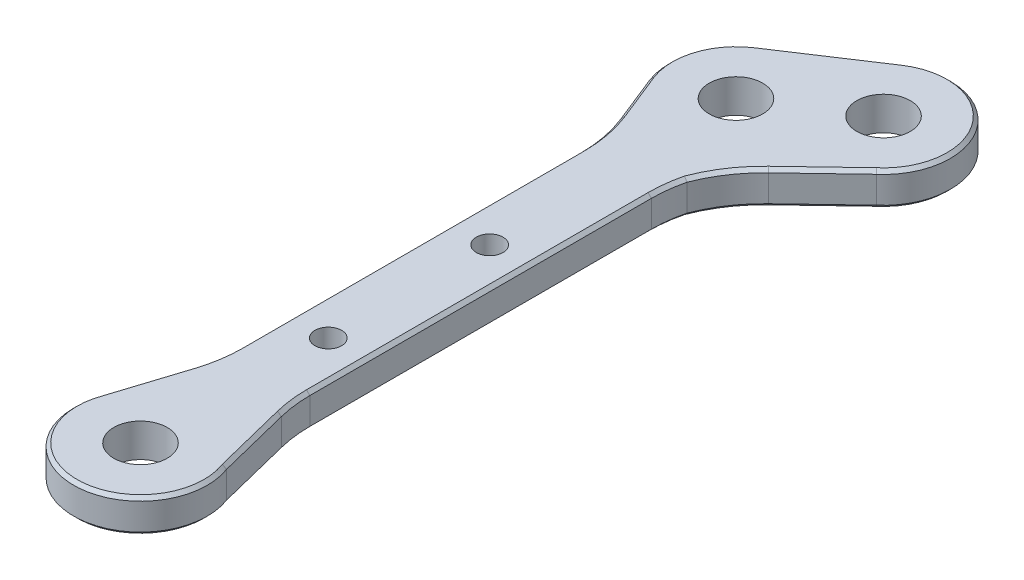
SolidWorks part; units mm, degrees
material "5052-O"
ref_plane "正面" through (0, 0, 0) normal (0, 0, 1) x (1, 0, 0)
ref_plane "平面" through (0, 0, 0) normal (0, 1, 0) x (1, 0, 0)
ref_plane "右側面" through (0, 0, 0) normal (1, 0, 0) x (0, 0, -1)
sketch "ｽｹｯﾁ1" plane through (0, 0, 0) normal (0, 1, 0) x (1, 0, 0)
  line L0 (-31.2667, 475.4743) -> (17.7329, 475.685) construction
  line L1 (29.4015, 408.0828) -> (36.0548, 412.4694)
  line L2 (29.6332, 396.7526) -> (27.4704, 402.1573)
  line L3 (29.6332, 396.7526) -> (29.6332, 367.7526)
  line L4 (29.6332, 367.7526) -> (27.5048, 361.084)
  line L5 (36.0548, 398.7723) -> (42.0644, 404.5017)
  line L6 (36.0548, 398.7723) -> (35.2069, 396.051)
  line L7 (35.2069, 396.051) -> (35.2069, 367.7526)
  line L8 (35.2069, 367.7526) -> (36.8714, 361.084)
  circle A0 centre (32.1537, 403.9084) radius 5
  circle A1 centre (38.807, 408.295) radius 5
  circle A2 centre (32.1881, 359.3329) radius 5
  circle A3 centre (32.42, 385.2182) radius 1
  circle A4 centre (32.42, 373.1465) radius 1
  circle A5 centre (32.1537, 403.9084) radius 2
  circle A6 centre (38.807, 408.295) radius 2
  circle A7 centre (32.1881, 359.3329) radius 2
  dimension "D1" = 49
extrude "ﾎﾞｽ - 押し出し1" add sketch "ｽｹｯﾁ1" along normal blind 2.5 contours A2 A7 | A2 L8 L7 L6 L5 A1 A0 L2 L3 L4 A4 A3 | A1 A0 L2 A5 | A1 L1 A0 | A0 A1 | A1 A0 A6 region at (31.5634, 0, -408.7311) region at (33.0399, 0, -409.8032) region at (41.1105, 0, -412.5729) region at (35.4804, 0, -406.1017) region at (32.6724, 0, -382.4425) region at (32.1881, 0, -364.1915)
fillet "ﾌｨﾚｯﾄ1" radius 10 2 edges at (35.2069, 1.25, -396.051) (36.0548, 1.25, -398.7723)
fillet "ﾌｨﾚｯﾄ2" radius 10 1 edges at (29.6332, 1.25, -396.7526)
fillet "ﾌｨﾚｯﾄ3" radius 10 2 edges at (29.6332, 1.25, -367.7526) (35.2069, 1.25, -367.7526)
chamfer "面取り1" distance 0.25 angle 45 15 edges at (39.9976, 2.5, -402.5313) (36.5064, 2.5, -398.8638) (35.2781, 2.5, -395.7205) (35.2069, 2.5, -381.7555) (35.2816, 2.5, -367.7618) (36.188, 2.5, -363.822) (32.1881, 2.5, -354.3329) (28.3322, 2.5, -363.6766) (29.5141, 2.5, -367.7711) (29.6332, 2.5, -382.0679) (29.4526, 2.5, -396.7178) (28.1939, 2.5, -400.3493) (27.3998, 2.5, -405.4577) (32.7281, 2.5, -410.2761) (42.7989, 2.5, -411.3059)
chamfer "面取り2" distance 0.25 angle 45 15 edges at (32.1881, 0, -354.3329) (36.188, 0, -363.822) (35.2816, 0, -367.7618) (28.3322, 0, -363.6766) (29.5141, 0, -367.7711) (35.2069, 0, -381.7555) (35.2781, 0, -395.7205) (36.5064, 0, -398.8638) (29.6332, 0, -382.0679) (29.4526, 0, -396.7178) (28.1939, 0, -400.3493) (27.3998, 0, -405.4577) (32.7281, 0, -410.2761) (42.7989, 0, -411.3059) (39.9976, 0, -402.5313)
